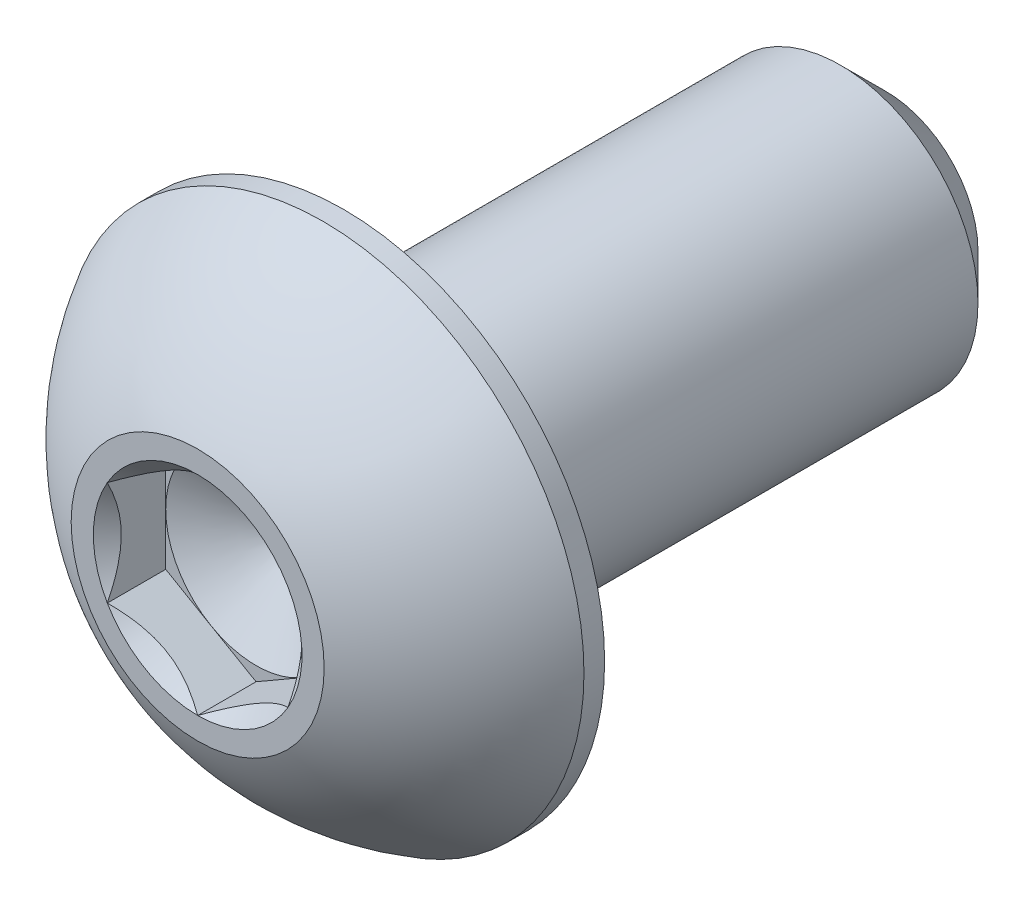
SolidWorks part; units mm, degrees
ref_plane "Front Plane" through (0, 0, 0) normal (0, 0, 1) x (1, 0, 0)
ref_plane "Top Plane" through (0, 0, 0) normal (0, 1, 0) x (1, 0, 0)
ref_plane "Right Plane" through (0, 0, 0) normal (1, 0, 0) x (0, 0, -1)
sketch "Sketch1" plane through (0, 0, 0) normal (1, 0, 0) x (0, 0, -1)
  line L0 (-6.0452, 0) -> (6.0452, 0) construction
  line L1 (-3.4798, 4.5847) -> (-3.4798, -4.5847) construction
  line L2 (-6.0452, 1.5875) -> (-6.0452, -1.5875) construction
  line L3 (6.0452, 2.413) -> (6.0452, -2.413) construction
  line L4 (5.9791, 2.5276) -> (6.5082, 1.611) construction
  line L5 (6.5082, 1.611) -> (7.0374, 2.5276) construction
  line L6 (7.0374, 2.5276) -> (5.9791, 2.5276) construction
  line L7 (6.5082, 2.5276) -> (6.5082, 2.413) construction
  line L8 (6.5082, 1.611) -> (6.5082, 1.7256) construction
  line L9 (6.4421, 1.7256) -> (6.5744, 1.7256)
  line L10 (-6.0452, 2.2225) -> (-6.0452, -2.2225) construction
  line L11 (-3.4798, 4.5847) -> (-3.8427, 4.5847) construction
  line L12 (-6.0452, 1.5875) -> (-5.019, 1.5875) construction
  line L13 (-5.019, 1.5875) -> (-4.1025, 0) construction
  point P5 (-3.4798, 0)
  point P10 (2.341, -2.413)
  dimension "Drive Size" = 3.175
  dimension "Head Diameter" = 9.1694
  dimension "Head Height" = 2.5654
  dimension "Diameter" = 4.826
  dimension "Thread Length" = 9.525
  dimension "D1" = 3.7042
  dimension "Pitch" = 1.0583
  dimension "D2" = 0.1323
  dimension "D3" = 4.445
  dimension "D4" = 0.3629
  dimension "D5" = 60
  dimension "D6" = 1.0262
sketch "Sketch2" plane through (0, 0, 0) normal (1, 0, 0) x (0, 0, -1)
  line L0 (-6.0452, 1.5875) -> (-6.0452, 2.2225)
  line L1 (-3.8427, 4.5847) -> (-3.4798, 4.5847)
  line L2 (-3.4798, 4.5847) -> (-3.4798, 2.413)
  line L3 (-3.4798, 4.5847) -> (-3.4798, -4.5847) construction
  line L4 (-3.4798, 2.413) -> (5.2515, 2.413)
  line L5 (6.0452, 1.6193) -> (6.0452, 0)
  line L6 (-6.0452, 1.5875) -> (-5.019, 1.5875)
  line L7 (-5.019, 1.5875) -> (-4.1025, 0)
  line L8 (6.0452, 0) -> (-4.1025, 0)
  line L9 (5.2515, 2.413) -> (6.0452, 1.6193)
  arc A0 (-3.8427, 4.5847) -> (-6.0452, 2.2225) centre (-1.2936, 0) ccw
  point P13 (6.0452, 2.413)
  dimension "D1" = 0.7937
  dimension "D2" = 45
revolve "Revolve1" add sketch "Sketch2" angle 360 about L0
sketch "Sketch3" plane through (0, 0, 0) normal (0, 0, 1) x (1, 0, 0)
  line L1 (0, 1.8331) -> (-1.5875, 0.9165)
  line L2 (-1.5875, 0.9165) -> (-1.5875, -0.9165)
  line L3 (-1.5875, -0.9165) -> (0, -1.8331)
  line L4 (0, -1.8331) -> (1.5875, -0.9165)
  line L5 (1.5875, -0.9165) -> (1.5875, 0.9165)
  line L6 (1.5875, 0.9165) -> (0, 1.8331)
  circle A0 centre (0, 0) radius 1.5875 construction
extrude "Cut-Extrude1" cut sketch "Sketch3" along normal through all from vertex starting at point (0, 1.5875, 5.019)
sketch "Sketch4" plane through (0, 0, 6.0452) normal (0, 0, 1) x (1, 0, 0)
  circle A0 centre (0, 0) radius 1.8331
extrude "Cut-Extrude2" cut sketch "Sketch4" against normal up to next (12.0904 mm away) draft 45
sketch "Sketch5" plane through (0, 0, -6.0452) normal (0, 0, -1) x (-1, 0, 0)
  circle A0 centre (0, 0) radius 2.413
curve "Helix/Spiral1" [suppressed] pitch 1.0583 height 10.5833 turns 10
sketch "Sketch6" plane through (0, 0, 0) normal (1, 0, 0) x (0, 0, -1)
  line L0 (6.0452, 2.413) -> (6.9712, 2.413)
  line L1 (6.9712, 2.413) -> (6.5744, 1.7256)
  line L2 (6.4421, 1.7256) -> (6.5744, 1.7256)
  line L3 (6.4421, 1.7256) -> (6.0452, 2.413)
  line L4 (6.5082, 1.611) -> (7.0374, 2.5276) construction
sweep "Sweep1" [suppressed] add profiles "Sketch6" path "Helix/Spiral1"
combine bodies "Combine1" [suppressed] operation type add bodies to combine 104 105
sketch "Sketch7" plane through (0, 0, 0) normal (1, 0, 0) x (0, 0, -1)
  line L0 (-5.019, 2.413) -> (-3.4798, 2.413)
  line L1 (-5.019, 2.413) -> (-5.019, 1.5875)
  line L2 (-5.019, 1.5875) -> (-4.1025, 0)
  line L3 (-4.1025, 0) -> (-1.2764, 0)
  line L5 (-3.4798, 4.5847) -> (-3.4798, -4.5847) construction
  line L6 (-3.4798, 2.413) -> (-1.2764, 1.611)
  line L7 (-1.2764, 1.611) -> (-1.2764, 0)
  dimension "D1" = 20
revolve "Revolve2" [suppressed] add sketch "Sketch7" angle 360 about L0
ref_axis "Center Axis 1" through (0, 0, -4.0714) along (0, 0, 1)
ref_plane "Contact Plane 1" through (0, 0, 3.4798) normal (0, 0, -1) x (-1, 0, 0)
equation "\"D2@Sketch1\"=\"Pitch@Sketch1\"*.125"
equation "\"D1@Sketch1\"=\"Pitch@Sketch1\"*3.5"
equation "\"D3@Sketch1\"=\"Drive Size@Sketch1\"*1.4"
equation "\"D4@Sketch1\"=(\"D3@Sketch1\"-\"Drive Size@Sketch1\")/3.5"
equation "\"D6@Sketch1\"=\"Head Height@Sketch1\"*.40"
equation "\"D1@Sketch2\"=\"Pitch@Sketch1\"*.750"
equation "\"D4@Helix/Spiral1\"=\"Pitch@Sketch1\""
equation "\"D3@Helix/Spiral1\"=\"D4@Helix/Spiral1\"+\"Thread Length@Sketch1\""
